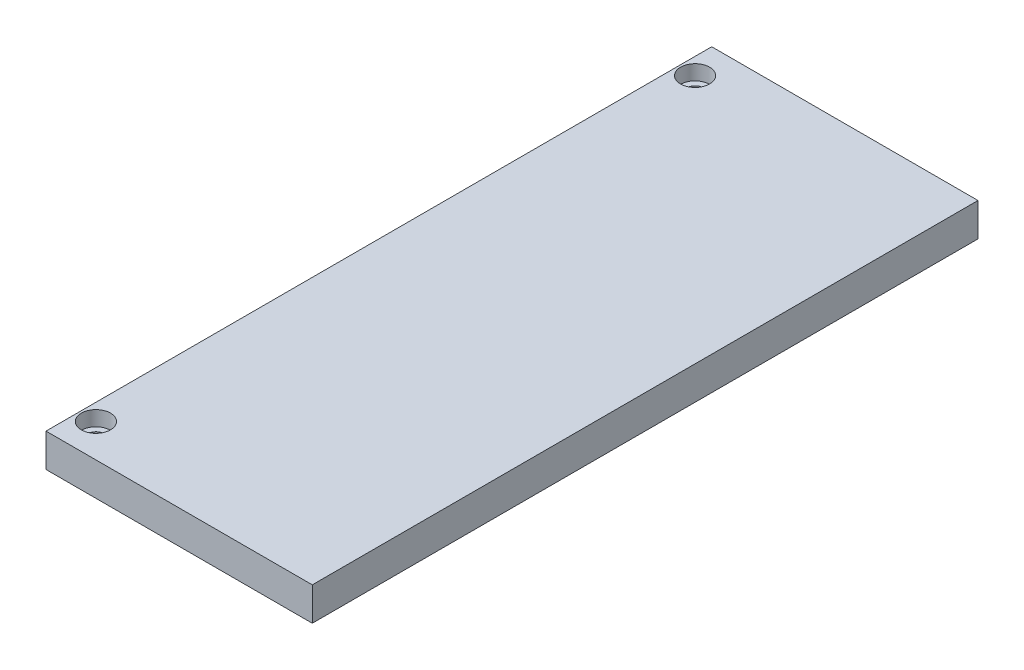
SolidWorks part; units mm, degrees
material "6061 Alloy"
ref_plane "Front Plane" through (0, 0, 0) normal (0, 0, 1) x (1, 0, 0)
ref_plane "Top Plane" through (0, 0, 0) normal (0, 1, 0) x (1, 0, 0)
ref_plane "Right Plane" through (0, 0, 0) normal (1, 0, 0) x (0, 0, -1)
sketch "Sketch1" plane through (0, 0, 0) normal (0, 1, 0) x (1, 0, 0)
  line L1 (-25.4, -63.5) -> (25.4, -63.5)
  line L2 (-25.4, -63.5) -> (-25.4, 63.5)
  line L3 (-25.4, 63.5) -> (25.4, 63.5)
  line L4 (25.4, -63.5) -> (25.4, 63.5)
  line L5 (-25.4, -63.5) -> (25.4, 63.5) construction
  line L6 (-25.4, 63.5) -> (25.4, -63.5) construction
  point P0 (0, 0)
  dimension "D1" = 127
  dimension "D2" = 50.8
extrude "Boss-Extrude1" add sketch "Sketch1" along normal blind 6.35
hole_wizard "CBORE for #4 Socket Head Cap Screw1" positions "Sketch2" profile "Sketch3" counterbore size "#4" standard "ANSI Inch" end condition through all
sketch "Sketch2" plane through (0, 6.35, 0) normal (0, 1, 0) x (1, 0, 0)
  line L0 (25.4, 63.5) -> (-25.4, 63.5) construction
  line L1 (-25.4, 63.5) -> (-25.4, -63.5) construction
  line L2 (-25.4, -63.5) -> (25.4, -63.5) construction
  point P0 (-22.225, -57.15)
  point P2 (-22.225, 57.15)
  dimension "D1" = 6.35
  dimension "D2" = 3.175
  dimension "D3" = 3.175
  dimension "D4" = 6.35
sketch "Sketch3" plane through (-22.225, 6.35, 57.15) normal (1, 0, 0) x (0, 0, 1)
  line L0 (0, 0) -> (0, 6.35)
  line L1 (0, 6.35) -> (1.6319, 6.35)
  line L3 (1.6319, 6.35) -> (1.6319, 2.8448)
  line L4 (1.6319, 2.8448) -> (2.7788, 2.8448)
  line L5 (2.7788, 2.8448) -> (2.7788, 0)
  line L7 (2.7788, 0) -> (0, 0)
  line L11 (0, -6.35) -> (0, 107.95) construction
  dimension "Thru Hole Dia." = 3.2639
  dimension "Thru Hole Depth" = 6.35
  dimension "C'Bore Dia." = 5.5575
  dimension "C'Bore Depth" = 2.8448
